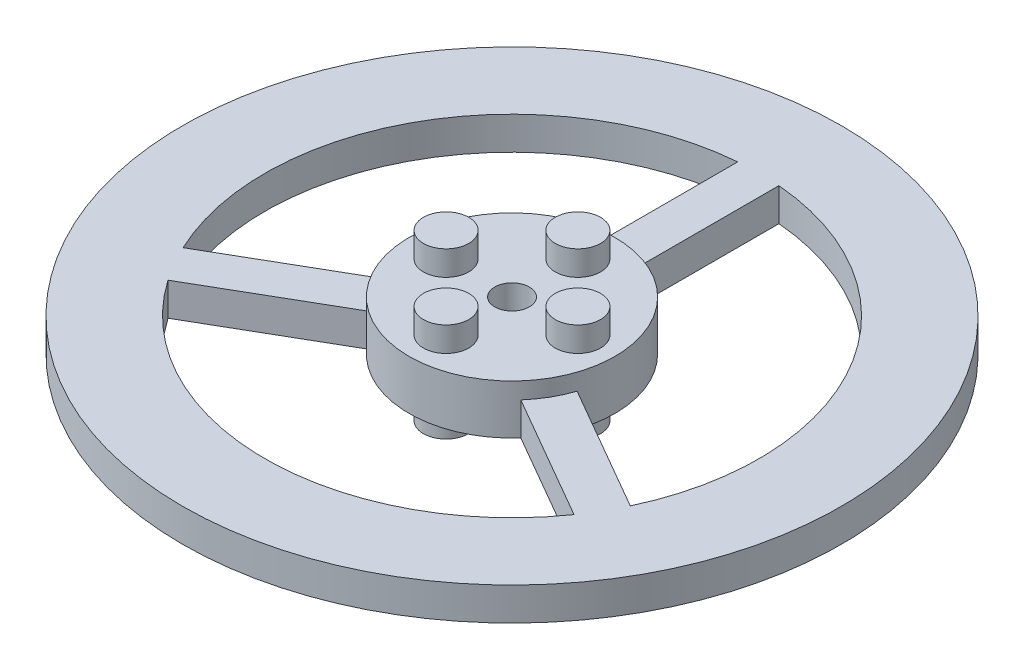
SolidWorks part; units mm, degrees
ref_plane "Plano frontal" through (0, 0, 0) normal (0, 0, 1) x (1, 0, 0)
ref_plane "Plano superior" through (0, 0, 0) normal (0, 1, 0) x (1, 0, 0)
ref_plane "Plano direito" through (0, 0, 0) normal (1, 0, 0) x (0, 0, -1)
sketch "Esboço1" plane through (0, 0, 0) normal (0, 1, 0) x (1, 0, 0)
  line L0 (0, 0) -> (0, 40) construction
  line L4 (34.641, -20) -> (0, 0) construction
  line L5 (0, 0) -> (-34.641, -20) construction
  line L6 (0, 0) -> (0, 35.257) construction
  line L9 (0, 0) -> (31.6917, -18.2972) construction
  line L12 (0, 0) -> (-31.6917, -18.2972) construction
  line L15 (-9.3566, -8.2888) -> (-24.6404, -17.1129)
  line L16 (-11.8566, -3.9587) -> (-27.1404, -12.7828)
  line L17 (-2.5, 12.2474) -> (-2.5, 29.8957)
  line L18 (2.5, 12.2474) -> (2.5, 29.8957)
  line L19 (11.8566, -3.9587) -> (27.1404, -12.7828)
  line L20 (9.3566, -8.2888) -> (24.6404, -17.1129)
  circle A0 centre (0, 0) radius 40
  arc A1 (-9.3566, -8.2888) -> (9.3566, -8.2888) centre (0, 0) ccw
  arc A2 (-24.6404, -17.1129) -> (24.6404, -17.1129) centre (0, 0) ccw
  arc A9 (11.8566, -3.9587) -> (2.5, 12.2474) centre (0, 0) ccw
  arc A10 (-2.5, 12.2474) -> (-11.8566, -3.9587) centre (0, 0) ccw
  arc A11 (27.1404, -12.7828) -> (2.5, 29.8957) centre (0, 0) ccw
  arc A12 (-2.5, 29.8957) -> (-27.1404, -12.7828) centre (0, 0) ccw
  point P5 (0, 17.6285)
  point P14 (15.8459, -9.1486)
  point P21 (-15.8459, -9.1486)
  dimension "D1" = 80
  dimension "D2" = 25
  dimension "D3" = 10
extrude "Ressalto-extrusão1" add sketch "Esboço1" along normal blind 4
sketch "Esboço2" plane through (0, 4, 0) normal (0, 1, 0) x (1, 0, 0)
  circle A0 centre (0, 0) radius 2.1
  dimension "D1" = 4.2
extrude "Corte-extrusão1" cut sketch "Esboço2" against normal blind 4
sketch "Esboço3" plane through (0, 4, 0) normal (0, 1, 0) x (1, 0, 0)
  circle A0 centre (0, 0) radius 12.5
  circle A1 centre (0, 0) radius 2.1
extrude "Ressalto-extrusão2" add sketch "Esboço3" along normal blind 2
sketch "Esboço4" plane through (0, 6, 0) normal (0, 1, 0) x (1, 0, 0)
  line L0 (0, 0) -> (0, 12.5) construction
  arc A0 (2.5, 12.2474) -> (-2.5, 12.2474) centre (0, 0) ccw construction
  circle A1 centre (0, 8) radius 2.75
  circle A2 centre (8, 0) radius 2.75
  circle A3 centre (0, -8) radius 2.75
  circle A4 centre (-8, 0) radius 2.75
  point P17 (0, 0)
  dimension "D1" = 5.5
  dimension "D2" = 8
  dimension "D3" = 4
extrude "Ressalto-extrusão3" add sketch "Esboço4" along normal blind 3 and the other way blind 9
